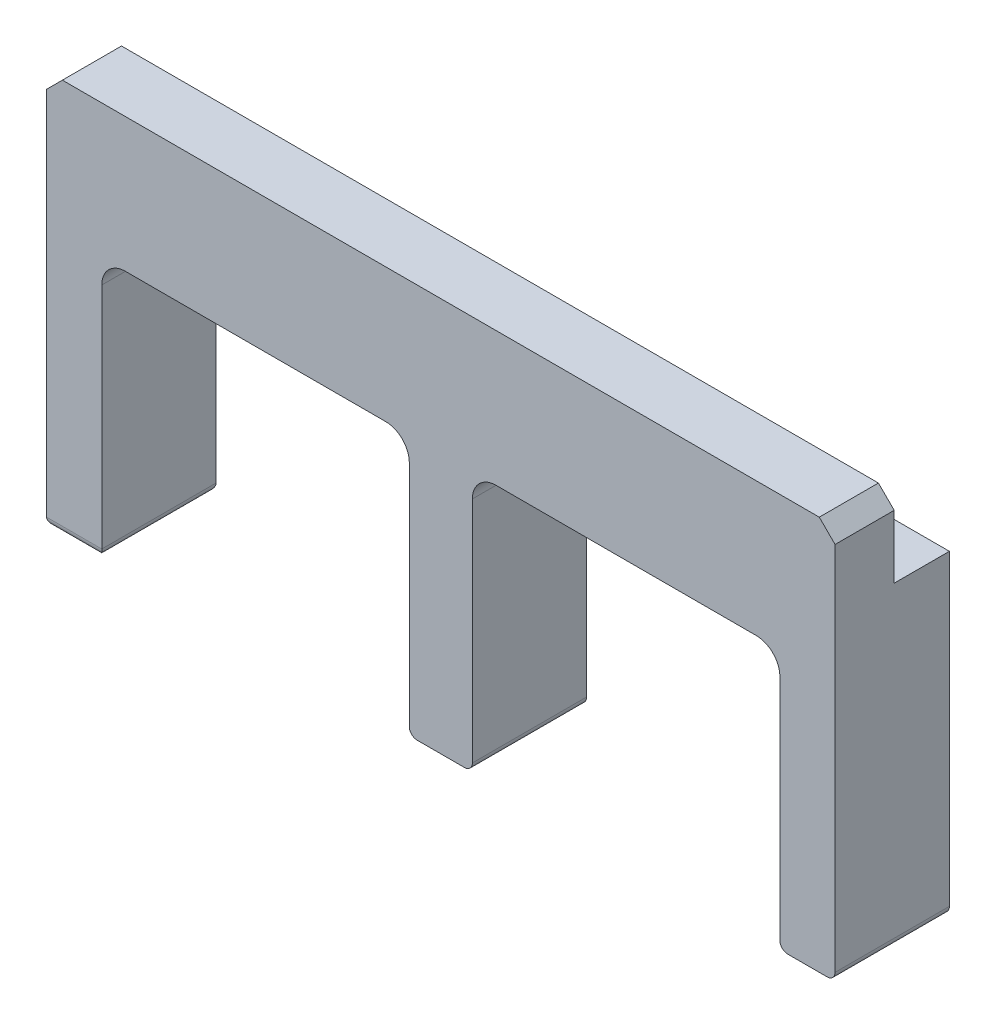
SolidWorks part; units mm, degrees
material "PLA2"
ref_plane "Front Plane" through (0, 0, 0) normal (0, 0, 1) x (1, 0, 0)
ref_plane "Top Plane" through (0, 0, 0) normal (0, 1, 0) x (1, 0, 0)
ref_plane "Right Plane" through (0, 0, 0) normal (1, 0, 0) x (0, 0, -1)
sketch "Sketch1" plane through (0, 0, 0) normal (1, 0, 0) x (0, 0, -1)
  line L0 (0, 0) -> (0, 12.7)
  line L1 (0, 12.7) -> (-9.525, 12.7)
  line L2 (-9.525, 12.7) -> (-9.525, -50.8)
  line L3 (-9.525, -50.8) -> (8.89, -50.8)
  line L4 (8.89, -50.8) -> (8.89, 0)
  line L5 (8.89, 0) -> (0, 0)
  dimension "D1" = 12.7
  dimension "D2" = 8.89
  dimension "D3" = 50.8
  dimension "D4" = 9.525
extrude "Boss-Extrude1" add sketch "Sketch1" along normal mid plane 127
sketch "Sketch2" plane through (0, 0, -8.89) normal (0, 0, -1) x (-1, 0, 0)
  line L0 (0, -50.8) -> (0, 12.7) construction
  line L1 (-63.5, -50.8) -> (63.5, -50.8) construction
  line L2 (-63.5, 12.7) -> (63.5, 12.7) construction
  line L3 (54.61, -8.89) -> (-54.61, -8.89)
  line L4 (-54.61, -8.89) -> (-54.61, -50.8)
  line L5 (-54.61, -50.8) -> (54.61, -50.8)
  line L6 (54.61, -8.89) -> (54.61, -50.8)
  line L7 (-63.5, -50.8) -> (-63.5, 0) construction
  line L8 (-63.5, 0) -> (63.5, 0) construction
  point P11 (0, -8.89)
  dimension "D1" = 8.89
  dimension "D2" = 8.89
extrude "Cut-Extrude1" cut sketch "Sketch2" against normal through all
sketch "Sketch3" plane through (0, 0, -8.89) normal (0, 0, -1) x (-1, 0, 0)
  line L0 (0, 0) -> (0, 50000) construction
  line L1 (5.08, -8.89) -> (-5.08, -8.89)
  line L2 (54.61, -8.89) -> (-54.61, -8.89) construction
  line L3 (-5.08, -8.89) -> (-5.08, -50.8)
  line L4 (-5.08, -50.8) -> (5.08, -50.8)
  line L5 (-63.5, -50.8) -> (49936.5, -50.8) construction
  line L7 (5.08, -8.89) -> (5.08, -50.8)
  point P12 (-6.8251, -39.996)
  point P14 (0, -50.8)
  point P15 (0, -8.89)
  dimension "D1" = 10.16
extrude "Boss-Extrude2" add sketch "Sketch3" against normal up to surface (18.415 mm away) up to face at (0, -24.4475, 9.525)
fillet "Fillet1" radius 3.81 4 edges at (-54.61, -8.89, 0.3175) (-5.08, -8.89, 0.3175) (5.08, -8.89, 0.3175) (54.61, -8.89, 0.3175)
chamfer "Chamfer1" distance 2.54 angle 45 2 edges at (-63.5, 12.7, 4.7625) (63.5, 12.7, 4.7625)
fillet "Fillet2" radius 1.27 8 edges at (-63.5, -50.8, 0.3175) (-59.055, -50.8, 9.525) (-54.61, -50.8, 0.3175) (-59.055, -50.8, -8.89) (-5.08, -50.8, 0.3175) (5.08, -50.8, 0.3175) (54.61, -50.8, 0.3175) (63.5, -50.8, 0.3175)
ref_plane "Plane1" through (59.055, 0, 0) normal (1, 0, 0) x (0, 0, -1)
ref_plane "Plane2" through (-59.055, 0, 0) normal (1, 0, 0) x (0, 0, -1)
ref_plane "Plane3" through (0, 0, 0.3175) normal (0, 0, 1) x (1, 0, 0)
